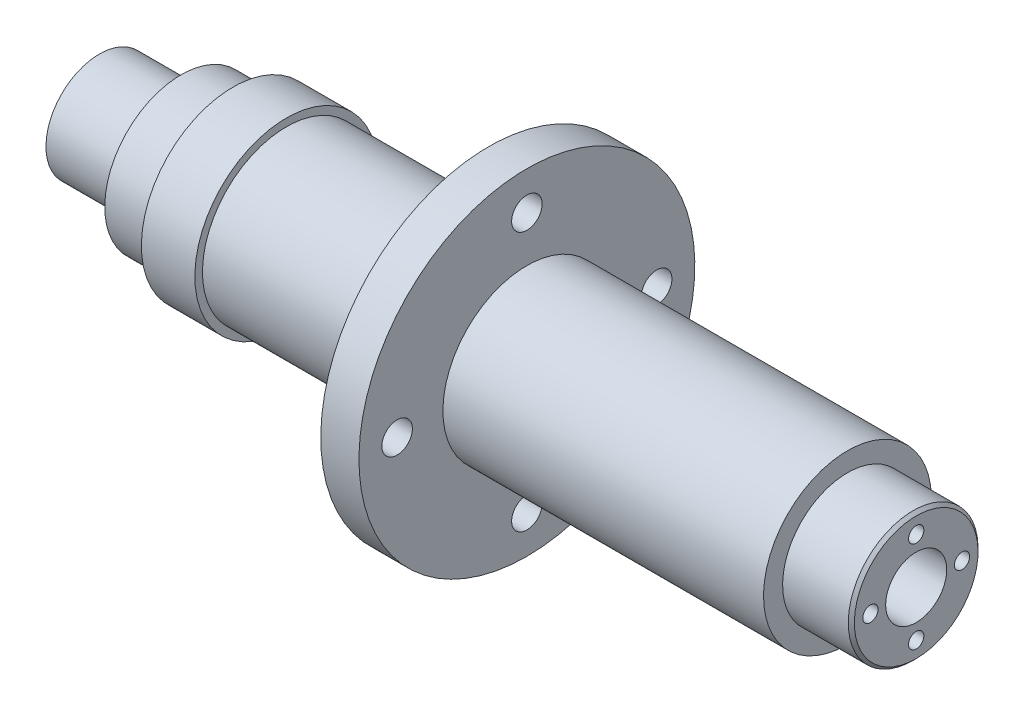
SolidWorks part; units mm, degrees
material "2024-T4"
ref_plane "Front Plane" through (0, 0, 0) normal (0, 0, 1) x (1, 0, 0)
ref_plane "Top Plane" through (0, 0, 0) normal (0, 1, 0) x (1, 0, 0)
ref_plane "Right Plane" through (0, 0, 0) normal (1, 0, 0) x (0, 0, -1)
other "Center of Mass" [suppressed]
sketch "Sketch3" plane through (0, 0, 0) normal (0, 0, 1) x (1, 0, 0)
  line L0 (0, 0) -> (0, 39.0464) construction
  line L1 (-72.5, 0) -> (72.5, 0) construction
  line L2 (-72.5, 2.5) -> (-72.5, 0) construction
  line L3 (-72.5, 2.5) -> (-72.5, 7)
  line L4 (-72.5, 7) -> (-62.3, 7)
  line L5 (-62.3, 7) -> (-62.3, 10)
  line L6 (-62.3, 10) -> (-55.5, 10)
  line L7 (-55.5, 10) -> (-55.5, 12)
  line L8 (-55.5, 12) -> (-38.5, 12)
  line L9 (-38.5, 12) -> (-38.5, 20)
  line L10 (-38.5, 20) -> (-26.5, 20)
  line L11 (-26.5, 20) -> (-26.5, 11)
  line L12 (-26.5, 11) -> (-21.5, 11)
  line L13 (3.5, 11) -> (3.5, 10)
  line L14 (3.5, 10) -> (35.5, 10)
  line L15 (35.5, 10) -> (35.5, 8.5)
  line L17 (72.5, 7.5) -> (72.5, 2.5)
  line L18 (72.5, 2.5) -> (-72.5, 2.5)
  line L19 (-32.5, 20) -> (-32.5, 2.5) construction
  line L20 (-11.5, 11) -> (-11.5, 2.5) construction
  line L21 (-77.5, 12) -> (-72.8417, 12) construction
  line L22 (-62.3, 10) -> (-62.3, 16) construction
  line L23 (-77.5, 15) -> (-72.8417, 15) construction
  line L24 (35.5, 8.5) -> (42.3, 8.5)
  line L25 (11.9511, 11) -> (20.8732, 11) construction
  line L26 (30.861, 12) -> (33.3773, 12) construction
  line L27 (42.3, 8.5) -> (42.3, 7.5)
  line L36 (42.3, 7.5) -> (72.5, 7.5)
  line L37 (-21.5, 11) -> (-21.5, 25)
  line L38 (35.5, 8.5) -> (44.5, 8.5) construction
  line L39 (-21.5, 25) -> (-16.5, 25)
  line L40 (-16.5, 25) -> (-16.5, 11)
  line L42 (-16.5, 11) -> (3.5, 11)
  point P5 (0, 0)
  dimension "D3" = 40
  dimension "D2" = 22
  dimension "D4" = 40
  dimension "D5" = 12
  dimension "D6" = 10.2
  dimension "D7" = 6.8
  dimension "D9" = 5
  dimension "D10" = 14
  dimension "D11" = 20
  dimension "D12" = 12
  dimension "D13" = 24
  dimension "D14" = 32
  dimension "D15" = 15
  dimension "D16" = 20
  dimension "D18" = 11
  dimension "D20" = 12
  dimension "D21" = 6.8
  dimension "D22" = 17
  dimension "D24" = 15
  dimension "D8" = 30
  dimension "D17" = 32
  dimension "D19" = 30.2
  dimension "D23" = 5
  dimension "D25" = 5
  dimension "D26" = 25
revolve "Revolve1" [suppressed] add sketch "Sketch3" angle 360 about L1
ref_plane "Plane1" [suppressed] through (0, 11, 0) normal (0, 1, 0) x (1, 0, 0)
sketch "Sketch4" [suppressed] plane through (0, 11, 0) normal (0, 1, 0) x (1, 0, 0)
  line L0 (3.5, 0) -> (-26.5, 0) construction
  line L1 (3.5, -11) -> (3.5, 11) construction
  line L2 (-26.5, -11) -> (-26.5, 11) construction
  line L3 (-11.5, 0) -> (-11.5, 23.5234) construction
  line L4 (72.5, -7.5) -> (72.5, 7.5) construction
  line L5 (72.5, 0) -> (62.5, 0) construction
  line L6 (-17.5, -2) -> (-5.5, -2)
  line L7 (-17.5, -2) -> (-17.5, 2)
  line L8 (-17.5, 2) -> (-5.5, 2)
  line L9 (-5.5, -2) -> (-5.5, 2)
  line L10 (-17.5, -2) -> (-5.5, 2) construction
  line L11 (-17.5, 2) -> (-5.5, -2) construction
  line L16 (56.5, -2) -> (68.5, -2)
  line L17 (56.5, -2) -> (56.5, 2)
  line L18 (56.5, 2) -> (68.5, 2)
  line L19 (68.5, -2) -> (68.5, 2)
  line L20 (56.5, -2) -> (68.5, 2) construction
  line L21 (56.5, 2) -> (68.5, -2) construction
  point P17 (62.5, 0)
  dimension "D1" = 12
  dimension "D2" = 4
  dimension "D3" = 10
  dimension "D4" = 12
  dimension "D5" = 4
fillet "Fillet1" [suppressed] radius 1
ref_plane "Plane2" [suppressed] through (0, 7.5, 0) normal (0, 1, 0) x (1, 0, 0)
sketch "Sketch5" [suppressed] plane through (0, 7.5, 0) normal (0, 1, 0) x (1, 0, 0)
  line L0 (68.5, -2) -> (68.5, 2) construction
  line L1 (56.5, -2) -> (68.5, -2) construction
  line L2 (56.5, -2) -> (56.5, 2) construction
  line L3 (56.5, 2) -> (68.5, 2) construction
  line L4 (68.5, -2) -> (68.5, 2)
  line L5 (56.5, -2) -> (68.5, -2)
  line L6 (56.5, -2) -> (56.5, 2)
  line L7 (56.5, 2) -> (68.5, 2)
sketch "Sketch6" plane through (0, 0, 0) normal (0, 0, 1) x (1, 0, 0)
  line L0 (-53.5, 0) -> (53.5, 0) construction
  line L1 (-53.5, 4) -> (-53.5, 7)
  line L2 (-53.5, 7) -> (-42.8, 7)
  line L3 (-42.8, 7) -> (-42.8, 10)
  line L4 (-42.8, 10) -> (-36, 10)
  line L5 (-36, 10) -> (-36, 12)
  line L6 (-36, 12) -> (-29, 12)
  line L7 (-29, 12) -> (-29, 11)
  line L8 (-29, 11) -> (-2.5, 11)
  line L9 (44.5, 11) -> (44.5, 8.5)
  line L10 (44.5, 8.5) -> (53.5, 8.5)
  line L11 (53.5, 8.5) -> (53.5, 4)
  line L12 (53.5, 4) -> (-53.5, 4)
  line L13 (7.5, 11) -> (7.5, 4) construction
  line L14 (-2.5, 11) -> (-2.5, 22)
  line L15 (-2.5, 22) -> (2.5, 22)
  line L16 (2.5, 22) -> (2.5, 11)
  line L17 (2.5, 11) -> (44.5, 11)
  point P4 (0, 0)
  dimension "D1" = 10.7
  dimension "D2" = 6.8
  dimension "D3" = 9
  dimension "D4" = 61
  dimension "D5" = 107
  dimension "D6" = 7
  dimension "D7" = 10
  dimension "D8" = 12
  dimension "D9" = 11
  dimension "D10" = 8.5
  dimension "D11" = 8
  dimension "D12" = 31.5
  dimension "D13" = 5
  dimension "D14" = 22
  dimension "D15" = 24.5
revolve "Revolve2" add sketch "Sketch6" angle 360 about L0
ref_plane "Plane3" through (0, 11, 0) normal (0, 1, 0) x (1, 0, 0)
sketch "Sketch8" [suppressed] plane through (-16.5, 0, 0) normal (1, 0, 0) x (0, 0, -1)
  line L0 (0, 0) -> (0, 17) construction
  circle A0 centre (0, 17) radius 2
  circle A1 centre (17, 0) radius 2
  circle A2 centre (0, -17) radius 2
  circle A3 centre (-17, 0) radius 2
  point P12 (0, 0)
  dimension "D1" = 4
  dimension "D3" = 17
  dimension "D4" = 17
  dimension "D5" = 34
  dimension "D2" = 4
extrude "Cut-Extrude5" [suppressed] cut sketch "Sketch8" against normal up to surface (5 mm away)
sketch "Sketch9" plane through (2.5, 0, 0) normal (1, 0, 0) x (0, 0, -1)
  line L0 (0, 0) -> (0, 17) construction
  circle A0 centre (0, 17) radius 2
  circle A1 centre (17, 0) radius 2
  circle A2 centre (0, -17) radius 2
  circle A3 centre (-17, 0) radius 2
  point P12 (0, 0)
  dimension "D1" = 4
  dimension "D2" = 17
  dimension "D4" = 17
  dimension "D5" = 17
  dimension "D3" = 4
extrude "Cut-Extrude6" cut sketch "Sketch9" against normal up to surface (5 mm away) up to face at (-2.5, -11, 0)
sketch "Sketch10" [suppressed] plane through (72.5, 0, 0) normal (1, 0, 0) x (0, 0, -1)
  circle A1 centre (0, 0) radius 7.5 construction
  circle A2 centre (0, 0) radius 7.5
extrude "Cut-Extrude7" [suppressed] cut sketch "Sketch10" against normal blind 15
sketch "Sketch11" [suppressed] plane through (57.5, 0, 0) normal (1, 0, 0) x (0, 0, -1)
  line L0 (0, 0) -> (0, 5) construction
  circle A0 centre (0, 5) radius 1.5
  circle A1 centre (5, 0) radius 1.5
  circle A2 centre (0, -5) radius 1.5
  circle A3 centre (-5, 0) radius 1.5
  point P12 (0, 0)
  dimension "D1" = 3
  dimension "D3" = 5
  dimension "D2" = 4
extrude "Cut-Extrude8" [suppressed] cut sketch "Sketch11" against normal blind 10
chamfer "Chamfer1" [suppressed] distance 3 angle 45
sketch "Sketch12" plane through (53.5, 0, 0) normal (1, 0, 0) x (0, 0, -1)
  line L0 (0, 0) -> (0, 6) construction
  circle A0 centre (0, 6) radius 1
  circle A1 centre (6, 0) radius 1
  circle A2 centre (0, -6) radius 1
  circle A3 centre (-6, 0) radius 1
  point P4 (-6.9771, 1.7431)
  point P5 (0, 0)
  point P13 (0, 0)
  dimension "D2" = 2
  dimension "D1" = 6
  dimension "D3" = 4
extrude "Cut-Extrude9" cut sketch "Sketch12" against normal blind 7
chamfer "Chamfer2" distance 0.4 angle 45 1 edges at (53.5, -8.5, 0)
equation "\"mainShaft-D\"= 20mm"
equation "\"mainTrackGear-D\"= 40mm"
equation "\"D4@Sketch3\"=\"wormGearL-D\""
equation "\"D11@Sketch3\"=\"mainShaft-D\""
equation "\"mini-flipper-shaft-diameter\"= 26mm"
equation "\"mini-shaft-ring-groove-diam\"= 7.8mm"
equation "\"mini-shaft-ring-groove-width\"= 1mm"
equation "\"dtCoverPlate-DistFrom-GearCent\"= 73mm"
equation "\"wormGearShaft-L\"= \"dtCoverPlate-DistFrom-GearCent\" - 27.75 + 3.75"
equation "\"wormGearShaft-Dsmall\"= 6mm"
equation "\"wormGearShaft-Dworm\"= 12mm"
equation "\"wormL-D\" = 12mm"
equation "\"wormR-D\" = 15mm"
equation "\"wormGearL-D\" = 40mm"
equation "\"wormGearR-D\" = 50mm"
